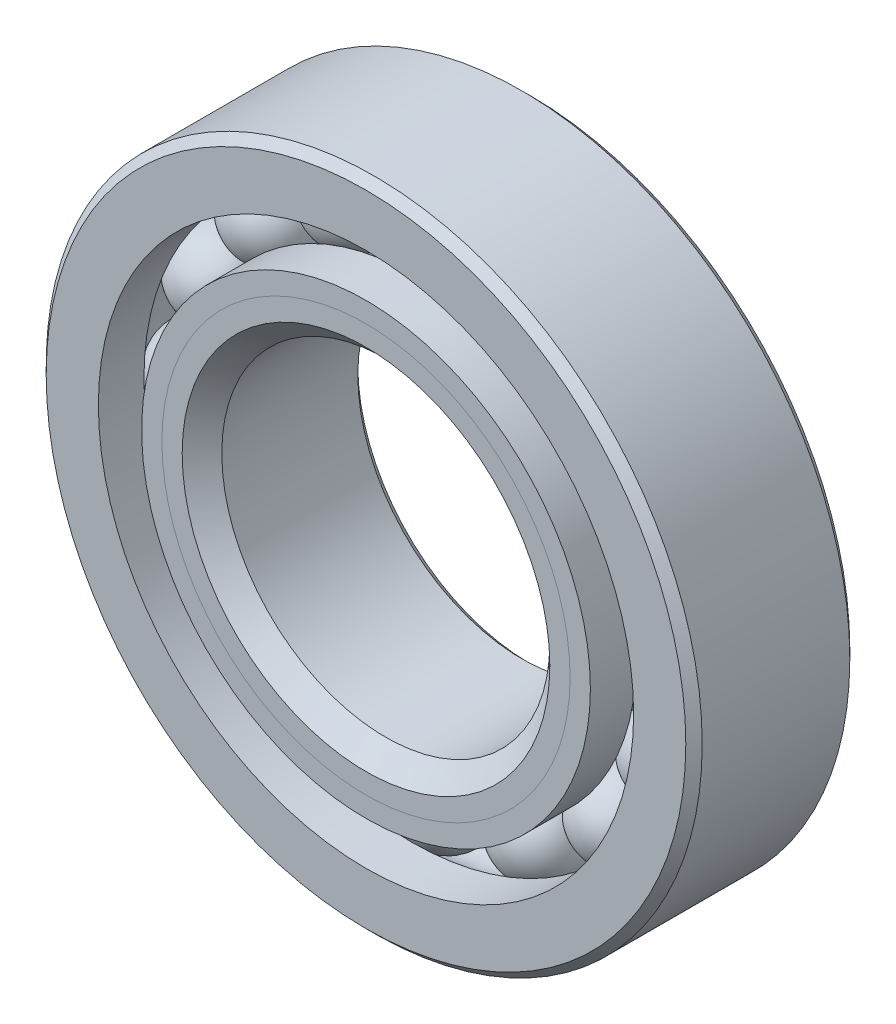
SolidWorks part; units mm, degrees
material "Plain Carbon Steel"
ref_plane "Front Plane" through (0, 0, 0) normal (0, 0, 1) x (1, 0, 0)
ref_plane "Top Plane" through (0, 0, 0) normal (0, 1, 0) x (1, 0, 0)
ref_plane "Right Plane" through (0, 0, 0) normal (1, 0, 0) x (0, 0, -1)
sketch "Sketch1" plane through (0, 0, 0) normal (1, 0, 0) x (0, 0, -1)
  line L0 (-1.5875, 0) -> (1.5875, 0) construction
  line L1 (0, 6.35) -> (0, -6.35) construction
  line L2 (1.4288, 6.35) -> (-1.4288, 6.35)
  line L3 (-1.4288, 6.35) -> (-1.5875, 6.1913)
  line L4 (-1.5875, 6.1913) -> (-1.5875, 5.1812)
  line L5 (-1.5875, 5.1812) -> (-0.7056, 5.1812)
  line L6 (1.5875, 5.1812) -> (0.7056, 5.1812)
  line L7 (1.5875, 6.1913) -> (1.5875, 5.1812)
  line L8 (1.4288, 6.35) -> (1.5875, 6.1913)
  line L9 (0, 6.35) -> (0, 4.7625) construction
  line L10 (0, 4.7625) -> (0, 3.175) construction
  arc A0 (-0.7056, 5.1812) -> (0.7056, 5.1812) centre (0, 4.7625) cw
  point P14 (0, 3.175)
  dimension "Width" = 3.175
  dimension "OD" = 12.7
  dimension "D1" = 45
  dimension "D2" = 0.1588
  dimension "D3" = 1.4111
  dimension "D4" = 0.4187
revolve "Revolve1" add sketch "Sketch1" angle 360 about L0
sketch "Sketch2" plane through (0, 0, 0) normal (1, 0, 0) x (0, 0, -1)
  line L0 (-1.5875, 4.3438) -> (-0.7056, 4.3438)
  line L1 (-1.5875, 6.1913) -> (-1.5875, -6.1913) construction
  line L2 (-1.5875, 4.3438) -> (-1.5875, 3.9512)
  line L3 (-1.5875, 3.9512) -> (-1.1949, 3.5585)
  line L4 (-1.1949, 3.5585) -> (0, 3.5585)
  line L5 (0, 6.35) -> (0, -6.35) construction
  line L6 (0, 3.5585) -> (0, 3.9421)
  line L7 (0, 3.9421) -> (0, 3.175) construction
  line L8 (-1.5875, 4.3438) -> (-1.5875, 3.5585) construction
  line L9 (-1.5875, 3.5585) -> (-1.1949, 3.5585) construction
  arc A0 (-0.7056, 4.3438) -> (0, 3.9421) centre (0, 4.7625) ccw
  arc A1 (0.7056, 5.1812) -> (-0.7056, 5.1812) centre (0, 4.7625) ccw construction
  circle A2 centre (0, 4.7625) radius 0.8204 construction
  dimension "D1" = 45
revolve "Revolve2" add sketch "Sketch2" angle 360 about L0
sketch "Sketch3" plane through (0, 0, 0) normal (1, 0, 0) x (0, 0, -1)
  line L0 (-1.5875, 3.9512) -> (-1.1949, 3.5585)
  line L1 (-1.1949, 3.5585) -> (0, 3.5585)
  line L2 (0, 3.5585) -> (0, 3.9421)
  line L3 (-1.5875, 3.9512) -> (-1.5875, 3.5585)
  line L4 (-1.5875, 4.3438) -> (-1.5875, 3.5585) construction
  line L5 (-1.5875, 3.5585) -> (-1.204, 3.175)
  line L6 (-1.204, 3.175) -> (1.4288, 3.175)
  line L7 (1.4288, 6.35) -> (1.4288, -6.35) construction
  line L8 (1.4288, 3.175) -> (1.5875, 3.3337)
  line L9 (1.5875, -6.1913) -> (1.5875, 6.1913) construction
  line L10 (1.5875, 3.3337) -> (1.5875, 4.3438)
  line L11 (1.5875, 4.3438) -> (0.7056, 4.3438)
  line L13 (1.4288, 6.35) -> (1.5875, 6.1913) construction
  circle A0 centre (0, 4.7625) radius 0.8204 construction
  arc A1 (0.7056, 4.3438) -> (0, 3.9421) centre (0, 4.7625) cw
revolve "Revolve3" add sketch "Sketch3" angle 360 about L0
sketch "Sketch4" plane through (0, 0, 0) normal (1, 0, 0) x (0, 0, -1)
  line L0 (-0.8204, 4.7625) -> (0.8204, 4.7625)
  circle A1 centre (0, 4.7625) radius 0.8204 construction
  arc A2 (-0.8204, 4.7625) -> (0.8204, 4.7625) centre (0, 4.7625) cw
  arc A3 (0.7056, 5.1812) -> (-0.7056, 5.1812) centre (0, 4.7625) ccw construction
revolve "Revolve4" add sketch "Sketch4" angle 360 about L0
ref_axis "Axis1" through (0, 0, -1.5875) along (0, 0, 1)
pattern_circular "CirPattern1" count 16 every 22.5 about axis through (0, 0, -1.5875) along (0, 0, 1) of bodies 104
equation "\"D2@Sketch1\" = \"Width@Sketch1\"*.05"
equation "\"D3@Sketch1\" = \"Width@Sketch1\"/2.25"
equation "\"D4@Sketch1\" = (((\"OD@Sketch1\"-\"Width@Sketch1\")/2)/3.25)/3.5"
equation "\"D2@CirPattern1\" = 360/\"Balls@CirPattern1\""
